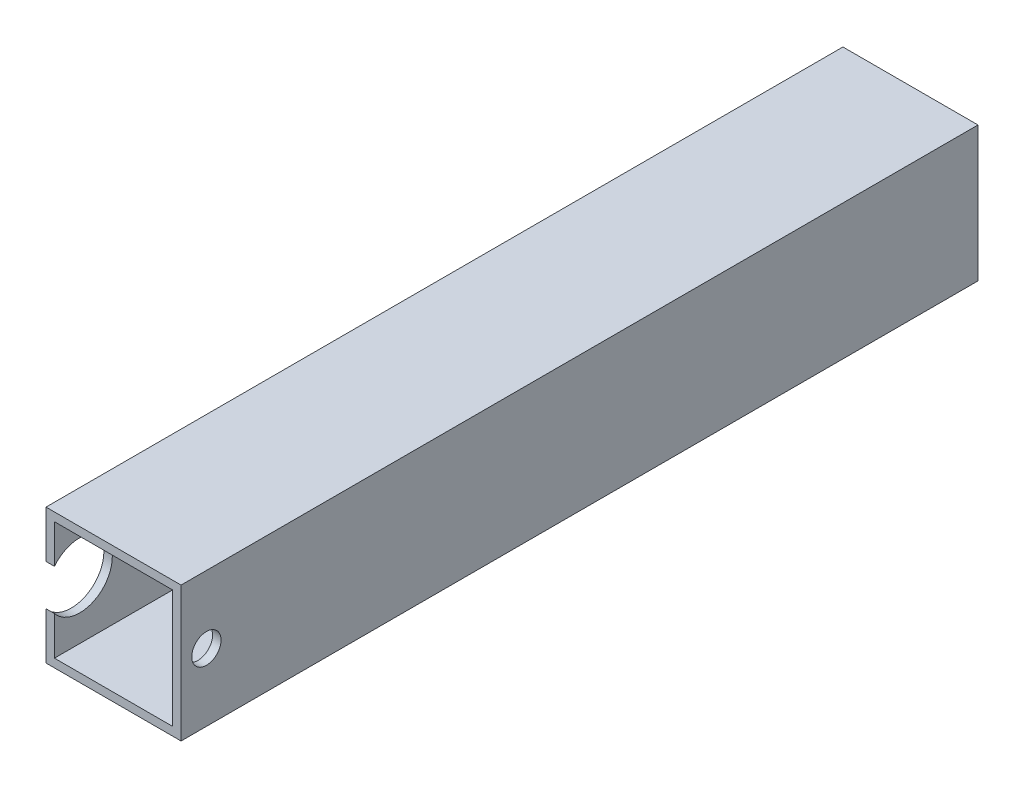
SolidWorks part; units mm, degrees
ref_plane "Front Plane" through (0, 0, 0) normal (0, 0, 1) x (1, 0, 0)
ref_plane "Top Plane" through (0, 0, 0) normal (0, 1, 0) x (1, 0, 0)
ref_plane "Right Plane" through (0, 0, 0) normal (1, 0, 0) x (0, 0, -1)
sketch "Sketch1" plane through (0, 0, 0) normal (0, 0, 1) x (1, 0, 0)
  line L1 (-12.7, -12.7) -> (12.7, -12.7)
  line L2 (-12.7, -12.7) -> (-12.7, 12.7)
  line L3 (-12.7, 12.7) -> (12.7, 12.7)
  line L4 (12.7, -12.7) -> (12.7, 12.7)
  line L5 (-12.7, -12.7) -> (12.7, 12.7) construction
  line L6 (-12.7, 12.7) -> (12.7, -12.7) construction
  point P0 (0, 0)
  dimension "D1" = 25.4
  dimension "D2" = 25.4
extrude "Boss-Extrude1" add sketch "Sketch1" along normal mid plane 149.86
shell "Shell1" thickness 1.5875 removed face at (0, 0, -74.93) removed face at (0, 0, 74.93)
hole_wizard "CBORE for M5 Hex Head Cap Screw1" positions "Sketch3" profile "Sketch2" counterbore size "M5" standard "ANSI Metric" end condition through all
sketch "Sketch3" plane through (-12.7, 0, 0) normal (-1, 0, 0) x (0, 0, 1)
  line L2 (74.93, 12.7) -> (74.93, -12.7) construction
  point P0 (70.1675, 0)
  dimension "D1" = 4.7625
sketch "Sketch2" plane through (-12.7, 0, 70.1675) normal (0, 1, 0) x (0, 0, 1)
  line L0 (0, 0) -> (0, 25.4)
  line L1 (0, 25.4) -> (2.75, 25.4)
  line L3 (2.75, 25.4) -> (2.75, 3.65)
  line L4 (2.75, 3.65) -> (6.12, 3.65)
  line L5 (6.12, 3.65) -> (6.12, 0)
  line L7 (6.12, 0) -> (0, 0)
  line L11 (0, -6.35) -> (0, 107.95) construction
  dimension "Thru Hole Dia." = 5.5
  dimension "Thru Hole Depth" = 25.4
  dimension "C'Bore Dia." = 12.24
  dimension "C'Bore Depth" = 3.65
